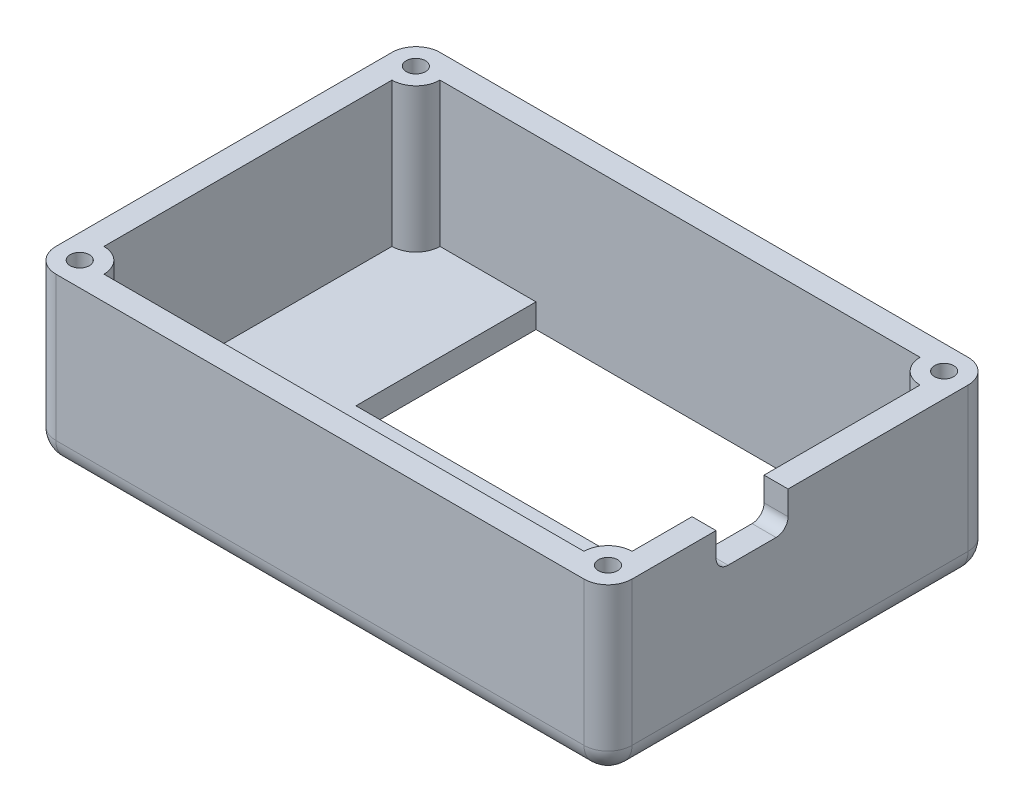
SolidWorks part; units mm, degrees
ref_plane "Front Plane" through (0, 0, 0) normal (0, 0, 1) x (1, 0, 0)
ref_plane "Top Plane" through (0, 0, 0) normal (0, 1, 0) x (1, 0, 0)
ref_plane "Right Plane" through (0, 0, 0) normal (1, 0, 0) x (0, 0, -1)
sketch "Sketch1" plane through (0, 0, 0) normal (0, 1, 0) x (1, 0, 0)
  line L0 (0, 0) -> (60.96, 0)
  line L1 (60.96, 0) -> (60.96, 40.64)
  line L2 (60.96, 40.64) -> (0, 40.64)
  line L3 (0, 40.64) -> (0, 0)
extrude "Boss-Extrude1" add sketch "Sketch1" along normal blind 17.78
shell "Shell1" thickness 2.54 removed face at (30.48, 17.78, -20.32)
sketch "Sketch2" plane through (0, 17.78, 0) normal (0, 1, 0) x (1, 0, 0)
  line L0 (58.42, 2.54) -> (58.42, 38.1) construction
  circle A0 centre (2.54, 2.54) radius 2.54
  circle A1 centre (58.42, 2.54) radius 2.54
  circle A2 centre (58.42, 38.1) radius 2.54
  circle A3 centre (2.54, 38.1) radius 2.54
extrude "Boss-Extrude2" add sketch "Sketch2" against normal blind 17.78
sketch "Sketch3" plane through (0, 17.78, 0) normal (0, 1, 0) x (1, 0, 0)
  circle A1 centre (2.5251, 38.1) radius 1.016
  circle A2 centre (2.5251, 2.54) radius 1.016
  circle A3 centre (58.42, 2.54) radius 1.016
  circle A4 centre (58.42, 38.1) radius 1.016
extrude "Cut-Extrude2" cut sketch "Sketch3" against normal blind 7.62
sketch "Sketch5" plane through (60.96, 0, 0) normal (1, 0, 0) x (0, 0, -1)
  line L0 (11.43, 17.78) -> (11.43, 13.97)
  line L1 (0, 17.78) -> (11.43, 17.78) construction
  line L2 (0, 17.78) -> (40.64, 17.78) construction
  line L3 (11.43, 13.97) -> (19.05, 13.97)
  line L4 (19.05, 13.97) -> (19.05, 17.78)
  line L5 (19.05, 17.78) -> (11.43, 17.78)
extrude "Cut-Extrude3" cut sketch "Sketch5" against normal blind 2.54
fillet "Fillet1" radius 1.27 2 edges at (59.69, 13.97, -19.05) (59.69, 13.97, -11.43)
sketch "Sketch6" plane through (0, 0, 0) normal (0, -1, 0) x (1, 0, 0)
  line L0 (60.96, 0) -> (60.96, -2.54) construction
  line L1 (60.96, 0) -> (60.96, -40.64) construction
  line L2 (60.96, -2.54) -> (55.88, -2.54) construction
  line L3 (55.88, -38.1) -> (55.88, -19.05)
  line L4 (60.96, -40.64) -> (55.88, -40.64) construction
  line L5 (60.96, -40.64) -> (0, -40.64) construction
  line L6 (55.88, -40.64) -> (55.88, -38.1) construction
  line L7 (55.88, -19.05) -> (15.24, -19.05)
  line L8 (15.24, -19.05) -> (15.24, -38.1)
  line L9 (15.24, -38.1) -> (55.88, -38.1)
extrude "Cut-Extrude4" cut sketch "Sketch6" against normal blind 2.54
fillet "Fillet3" radius 2.54 8 edges at (60.96, 0, -20.32) (60.96, 8.89, -40.64) (30.48, 0, -40.64) (0, 8.89, -40.64) (0, 8.89, 0) (0, 0, -20.32) (30.48, 0, 0) (60.96, 8.89, 0)
